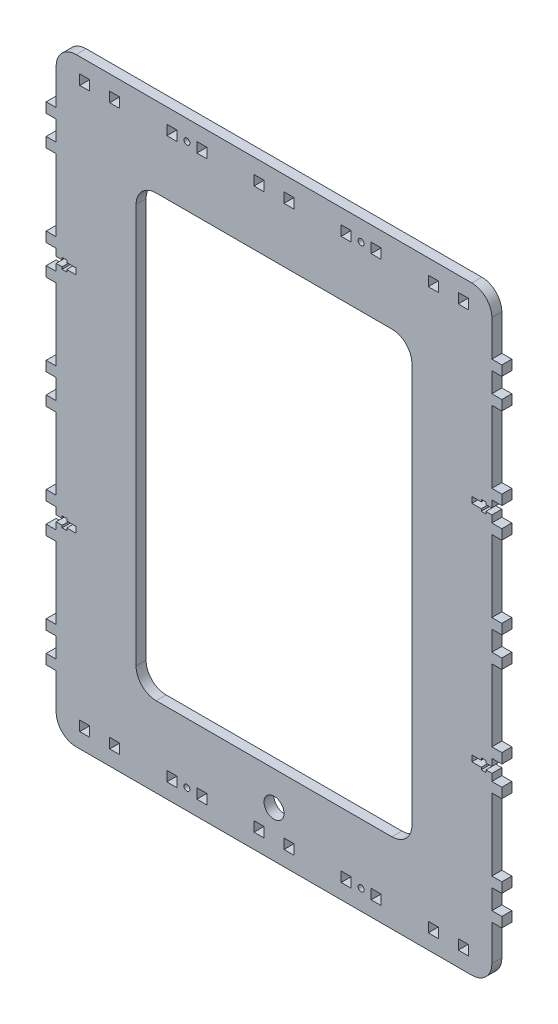
SolidWorks part; units mm, degrees
ref_plane "Front Plane" through (0, 0, 0) normal (0, 0, 1) x (1, 0, 0)
ref_plane "Top Plane" through (0, 0, 0) normal (0, 1, 0) x (1, 0, 0)
ref_plane "Right Plane" through (0, 0, 0) normal (1, 0, 0) x (0, 0, -1)
sketch "Sketch1" plane through (0, 0, 0) normal (0, 0, 1) x (1, 0, 0)
  line L0 (-109, -140) -> (109, -140) construction
  line L1 (109, 140) -> (109, 122)
  line L2 (-92.2, -140) -> (-82.2, -140) construction
  line L3 (-109, 140) -> (109, 140) construction
  line L5 (-92.2, -137.5) -> (-97.2, -137.5)
  line L6 (-92.2, -137.5) -> (-92.2, -142.5)
  line L7 (-99, -150) -> (99, -150)
  line L8 (-92.2, -142.5) -> (-97.2, -142.5)
  line L9 (-97.2, -137.5) -> (-97.2, -142.5)
  line L10 (-82.2, -137.5) -> (-77.2, -137.5)
  line L11 (-82.2, -137.5) -> (-82.2, -142.5)
  line L12 (-82.2, -142.5) -> (-77.2, -142.5)
  line L13 (-77.2, -137.5) -> (-77.2, -142.5)
  line L14 (-87.2, -140) -> (-87.2, -133.0276) construction
  line L15 (-48.6, -140) -> (-38.6, -140) construction
  line L16 (-109, -140) -> (-109, -122)
  line L17 (-99, 150) -> (99, 150)
  line L19 (-48.6, -137.5) -> (-53.6, -137.5)
  line L20 (-48.6, -137.5) -> (-48.6, -142.5)
  line L21 (-48.6, -142.5) -> (-53.6, -142.5)
  line L22 (-53.6, -137.5) -> (-53.6, -142.5)
  line L23 (-38.6, -137.5) -> (-33.6, -137.5)
  line L24 (-38.6, -137.5) -> (-38.6, -142.5)
  line L25 (-38.6, -142.5) -> (-33.6, -142.5)
  line L26 (-33.6, -137.5) -> (-33.6, -142.5)
  line L27 (-43.6, -140) -> (-43.6, -133.0276) construction
  line L28 (-5, -140) -> (5, -140) construction
  line L30 (-5, -137.5) -> (-10, -137.5)
  line L32 (-5, -137.5) -> (-5, -142.5)
  line L33 (-5, -142.5) -> (-10, -142.5)
  line L34 (-10, -137.5) -> (-10, -142.5)
  line L35 (5, -137.5) -> (10, -137.5)
  line L36 (5, -137.5) -> (5, -142.5)
  line L37 (5, -142.5) -> (10, -142.5)
  line L38 (10, -137.5) -> (10, -142.5)
  line L39 (0, -140) -> (0, -133.0276) construction
  line L40 (38.6, -140) -> (48.6, -140) construction
  line L41 (38.6, -137.5) -> (33.6, -137.5)
  line L42 (38.6, -137.5) -> (38.6, -142.5)
  line L43 (38.6, -142.5) -> (33.6, -142.5)
  line L44 (33.6, -137.5) -> (33.6, -142.5)
  line L45 (48.6, -137.5) -> (53.6, -137.5)
  line L46 (48.6, -137.5) -> (48.6, -142.5)
  line L47 (48.6, -142.5) -> (53.6, -142.5)
  line L48 (-109, -108) -> (-109, -117)
  line L49 (53.6, -137.5) -> (53.6, -142.5)
  line L50 (0, 182.823) -> (0, -174.5679) construction
  line L51 (43.6, -140) -> (43.6, -133.0276) construction
  line L52 (82.2, -140) -> (92.2, -140) construction
  line L53 (82.2, -137.5) -> (77.2, -137.5)
  line L54 (82.2, -137.5) -> (82.2, -142.5)
  line L55 (82.2, -142.5) -> (77.2, -142.5)
  line L56 (77.2, -137.5) -> (77.2, -142.5)
  line L57 (92.2, -137.5) -> (97.2, -137.5)
  line L58 (92.2, -137.5) -> (92.2, -142.5)
  line L59 (92.2, -142.5) -> (97.2, -142.5)
  line L60 (97.2, -137.5) -> (97.2, -142.5)
  line L61 (87.2, -140) -> (87.2, -133.0276) construction
  line L62 (-129.5738, 0) -> (-109, 0) construction
  line L63 (82.2, 140) -> (92.2, 140) construction
  line L64 (38.6, 140) -> (48.6, 140) construction
  line L65 (-5, 140) -> (5, 140) construction
  line L66 (-48.6, 140) -> (-38.6, 140) construction
  line L67 (-92.2, 140) -> (-82.2, 140) construction
  line L68 (97.2, 137.5) -> (97.2, 142.5)
  line L70 (92.2, 142.5) -> (97.2, 142.5)
  line L71 (92.2, 137.5) -> (92.2, 142.5)
  line L73 (92.2, 137.5) -> (97.2, 137.5)
  line L74 (77.2, 137.5) -> (77.2, 142.5)
  line L77 (82.2, 142.5) -> (77.2, 142.5)
  line L78 (82.2, 137.5) -> (82.2, 142.5)
  line L79 (82.2, 137.5) -> (77.2, 137.5)
  line L80 (53.6, 137.5) -> (53.6, 142.5)
  line L81 (48.6, 142.5) -> (53.6, 142.5)
  line L82 (48.6, 137.5) -> (48.6, 142.5)
  line L84 (48.6, 137.5) -> (53.6, 137.5)
  line L86 (33.6, 137.5) -> (33.6, 142.5)
  line L89 (38.6, 142.5) -> (33.6, 142.5)
  line L92 (38.6, 137.5) -> (38.6, 142.5)
  line L93 (38.6, 137.5) -> (33.6, 137.5)
  line L94 (10, 137.5) -> (10, 142.5)
  line L95 (5, 142.5) -> (10, 142.5)
  line L97 (5, 137.5) -> (5, 142.5)
  line L98 (5, 137.5) -> (10, 137.5)
  line L99 (-10, 137.5) -> (-10, 142.5)
  line L100 (-5, 142.5) -> (-10, 142.5)
  line L101 (-5, 137.5) -> (-5, 142.5)
  line L102 (-5, 137.5) -> (-10, 137.5)
  line L103 (-33.6, 137.5) -> (-33.6, 142.5)
  line L104 (-38.6, 142.5) -> (-33.6, 142.5)
  line L105 (-38.6, 137.5) -> (-38.6, 142.5)
  line L106 (-38.6, 137.5) -> (-33.6, 137.5)
  line L107 (-53.6, 137.5) -> (-53.6, 142.5)
  line L108 (-48.6, 142.5) -> (-53.6, 142.5)
  line L109 (-48.6, 137.5) -> (-48.6, 142.5)
  line L110 (-48.6, 137.5) -> (-53.6, 137.5)
  line L111 (-77.2, 137.5) -> (-77.2, 142.5)
  line L112 (-82.2, 142.5) -> (-77.2, 142.5)
  line L113 (-82.2, 137.5) -> (-82.2, 142.5)
  line L114 (-82.2, 137.5) -> (-77.2, 137.5)
  line L115 (-97.2, 137.5) -> (-97.2, 142.5)
  line L116 (-92.2, 142.5) -> (-97.2, 142.5)
  line L117 (-92.2, 137.5) -> (-92.2, 142.5)
  line L118 (-92.2, 137.5) -> (-97.2, 137.5)
  line L119 (109, 0) -> (97.7792, 0) construction
  line L120 (59, -110) -> (-59, -110)
  line L121 (69, -100) -> (69, 100)
  line L122 (59, 110) -> (-59, 110)
  line L123 (-69, -100) -> (-69, 100)
  line L124 (69, -110) -> (-69, 110) construction
  line L125 (69, 110) -> (-69, -110) construction
  line L126 (109, -1.5) -> (109, -5)
  line L127 (114, -5) -> (114, -10)
  line L128 (114, -10) -> (109, -10)
  line L129 (114, -5) -> (109, -5)
  line L130 (109, 1.5) -> (109, 5)
  line L131 (109, 5) -> (114, 5)
  line L132 (114, 5) -> (114, 10)
  line L133 (114, 10) -> (109, 10)
  line L134 (109, -1.5) -> (109, 1.5) construction
  line L135 (109, 5) -> (109, -5)
  line L136 (109, -10) -> (109, -46)
  line L137 (109, -51) -> (109, -54.5)
  line L138 (109, -66) -> (109, -102)
  line L139 (109, -57.5) -> (109, -61)
  line L140 (109, -122) -> (109, -140)
  line L141 (109, -107) -> (109, -117)
  line L142 (-109, 122) -> (-109, 140)
  line L143 (-109, 117) -> (-109, 107)
  line L144 (-109, 107) -> (-109, 117)
  line L145 (-109, 102) -> (-109, 66)
  line L146 (99, 0) -> (109, 0) construction
  line L147 (109, 56) -> (95.1587, 56) construction
  line L148 (109, 54.5) -> (109, 51)
  line L149 (114, 51) -> (114, 46)
  line L150 (114, 46) -> (109, 46)
  line L151 (114, 51) -> (109, 51)
  line L152 (109, 57.5) -> (109, 61)
  line L153 (109, 61) -> (114, 61)
  line L154 (114, 61) -> (114, 66)
  line L155 (114, 66) -> (109, 66)
  line L156 (109, 54.5) -> (109, 57.5) construction
  line L157 (109, 57.5) -> (106, 57.5)
  line L158 (103.7, 57.5) -> (103.7, 58.6)
  line L159 (106, 53.4) -> (103.7, 53.4)
  line L160 (106, 58.6) -> (106, 57.5)
  line L161 (103.7, 57.5) -> (99, 57.5)
  line L162 (99, 57.5) -> (99, 54.5)
  line L163 (99, 54.5) -> (103.7, 54.5)
  line L164 (106, 54.5) -> (106, 53.4)
  line L165 (103.7, 58.6) -> (106, 58.6)
  line L166 (103.7, 53.4) -> (103.7, 54.5)
  line L167 (106, 54.5) -> (109, 54.5)
  line L168 (99, 56) -> (109, 56) construction
  line L169 (109, 113.5) -> (109, 110.5)
  line L170 (109, 110.5) -> (109, 107)
  line L171 (114, 107) -> (114, 102)
  line L172 (114, 102) -> (109, 102)
  line L173 (114, 107) -> (109, 107)
  line L174 (109, 113.5) -> (109, 117)
  line L175 (109, 117) -> (114, 117)
  line L176 (114, 117) -> (114, 122)
  line L177 (114, 122) -> (109, 122)
  line L178 (109, 110.5) -> (109, 113.5) construction
  line L179 (109, 102) -> (109, 66)
  line L180 (-109, 66) -> (-109, 102)
  line L181 (-109, 61) -> (-109, 57.5)
  line L182 (-109, 51) -> (-109, 54.5)
  line L183 (-109, 46) -> (-109, 10)
  line L184 (-109, 54.5) -> (-109, 51)
  line L185 (-109, 57.5) -> (-109, 61)
  line L186 (-109, 10) -> (-109, 46)
  line L187 (-109, 5) -> (-109, -5)
  line L188 (-69, 0) -> (129.5738, 0) construction
  line L189 (-109, -5) -> (-109, 5)
  line L190 (-109, -10) -> (-109, -46)
  line L191 (-109, -46) -> (-109, -10)
  line L192 (109, -110.5) -> (109, -113.5) construction
  line L193 (81.3867, -112) -> (79.0545, -112) construction
  line L194 (-109, -51) -> (-109, -54.5)
  line L195 (-109, -61) -> (-109, -57.5)
  line L196 (99, -56) -> (95.1587, -56) construction
  line L197 (-109, -66) -> (-109, -102)
  line L198 (-109, -57.5) -> (-109, -61)
  line L199 (-109, -54.5) -> (-109, -51)
  line L200 (-109, -102) -> (-109, -66)
  line L201 (-109, -107) -> (-109, -117)
  line L202 (-109, -117) -> (-109, -107)
  line L203 (-109, -122) -> (-109, -150)
  line L204 (-109, -122) -> (-109, -140)
  line L205 (109, 102) -> (109, 66)
  line L206 (109, 61) -> (109, 51)
  line L207 (109, 46) -> (109, 10)
  line L208 (114, -122) -> (109, -122)
  line L209 (114, -117) -> (114, -122)
  line L210 (109, -117) -> (114, -117)
  line L211 (109, -113.5) -> (109, -117)
  line L212 (114, -107) -> (109, -107)
  line L213 (114, -102) -> (109, -102)
  line L214 (114, -107) -> (114, -102)
  line L215 (109, -110.5) -> (109, -107)
  line L216 (106, -54.5) -> (109, -54.5)
  line L217 (103.7, -53.4) -> (103.7, -54.5)
  line L218 (103.7, -58.6) -> (106, -58.6)
  line L219 (106, -54.5) -> (106, -53.4)
  line L220 (99, -54.5) -> (103.7, -54.5)
  line L221 (99, -57.5) -> (99, -54.5)
  line L222 (103.7, -57.5) -> (99, -57.5)
  line L223 (106, -58.6) -> (106, -57.5)
  line L224 (106, -53.4) -> (103.7, -53.4)
  line L225 (103.7, -57.5) -> (103.7, -58.6)
  line L226 (109, -57.5) -> (106, -57.5)
  line L227 (114, -66) -> (109, -66)
  line L228 (114, -61) -> (114, -66)
  line L229 (-109, -150) -> (69, 94.9541) construction
  line L230 (-109, 150) -> (109, -150) construction
  line L231 (109, -61) -> (114, -61)
  line L232 (109, -57.5) -> (109, -61)
  line L233 (114, -51) -> (109, -51)
  line L234 (114, -46) -> (109, -46)
  line L235 (114, -51) -> (114, -46)
  line L236 (109, -54.5) -> (109, -51)
  line L237 (-99, -56) -> (-95.1587, -56) construction
  line L241 (-109, -110.5) -> (-109, -113.5) construction
  line L244 (-109, 110.5) -> (-109, 113.5) construction
  line L248 (-99, 56) -> (-95.1587, 56) construction
  line L250 (-109, -1.5) -> (-109, 1.5) construction
  line L252 (-109, -54.5) -> (-109, -51)
  line L253 (-114, -51) -> (-114, -46)
  line L254 (-114, -46) -> (-109, -46)
  line L255 (-114, -51) -> (-109, -51)
  line L256 (-109, -57.5) -> (-109, -61)
  line L257 (-109, -61) -> (-114, -61)
  line L258 (-114, -61) -> (-114, -66)
  line L259 (-114, -66) -> (-109, -66)
  line L260 (-109, -57.5) -> (-106, -57.5)
  line L261 (-103.7, -57.5) -> (-103.7, -58.6)
  line L262 (-106, -53.4) -> (-103.7, -53.4)
  line L263 (-106, -58.6) -> (-106, -57.5)
  line L264 (-103.7, -57.5) -> (-99, -57.5)
  line L265 (-99, -57.5) -> (-99, -54.5)
  line L266 (-99, -54.5) -> (-103.7, -54.5)
  line L267 (-106, -54.5) -> (-106, -53.4)
  line L268 (-103.7, -58.6) -> (-106, -58.6)
  line L269 (-103.7, -53.4) -> (-103.7, -54.5)
  line L270 (-106, -54.5) -> (-109, -54.5)
  line L271 (-109, -110.5) -> (-109, -107)
  line L272 (-114, -107) -> (-114, -102)
  line L273 (-114, -102) -> (-109, -102)
  line L274 (-114, -107) -> (-109, -107)
  line L275 (-109, -113.5) -> (-109, -117)
  line L276 (-109, -117) -> (-114, -117)
  line L277 (-114, -117) -> (-114, -122)
  line L278 (-114, -122) -> (-109, -122)
  line L301 (-114, 122) -> (-109, 122)
  line L302 (-114, 117) -> (-114, 122)
  line L303 (-109, 117) -> (-114, 117)
  line L304 (-109, 113.5) -> (-109, 117)
  line L305 (-114, 107) -> (-109, 107)
  line L306 (-114, 102) -> (-109, 102)
  line L307 (-114, 107) -> (-114, 102)
  line L308 (-109, 110.5) -> (-109, 107)
  line L309 (-106, 54.5) -> (-109, 54.5)
  line L310 (-103.7, 53.4) -> (-103.7, 54.5)
  line L311 (-103.7, 58.6) -> (-106, 58.6)
  line L312 (-106, 54.5) -> (-106, 53.4)
  line L313 (-99, 54.5) -> (-103.7, 54.5)
  line L314 (-99, 57.5) -> (-99, 54.5)
  line L315 (-103.7, 57.5) -> (-99, 57.5)
  line L316 (-106, 58.6) -> (-106, 57.5)
  line L317 (-106, 53.4) -> (-103.7, 53.4)
  line L318 (-103.7, 57.5) -> (-103.7, 58.6)
  line L319 (-109, 57.5) -> (-106, 57.5)
  line L320 (-114, 66) -> (-109, 66)
  line L321 (-114, 61) -> (-114, 66)
  line L322 (-109, 61) -> (-114, 61)
  line L323 (-109, 57.5) -> (-109, 61)
  line L324 (-114, 51) -> (-109, 51)
  line L325 (-114, 46) -> (-109, 46)
  line L326 (-114, 51) -> (-114, 46)
  line L327 (-109, 54.5) -> (-109, 51)
  line L339 (-114, 10) -> (-109, 10)
  line L340 (-114, 5) -> (-114, 10)
  line L341 (-109, 5) -> (-114, 5)
  line L342 (-109, 1.5) -> (-109, 5)
  line L343 (-114, -5) -> (-109, -5)
  line L344 (-114, -10) -> (-109, -10)
  line L345 (-114, -5) -> (-114, -10)
  line L346 (-109, -1.5) -> (-109, -5)
  line L347 (-109, 150) -> (-109, 122)
  line L348 (109, 117) -> (109, 107)
  line L349 (101.7333, 140) -> (109, 150) construction
  circle A1 centre (0, -126.8749) radius 5
  circle A3 centre (-43.6, -140) radius 1.5
  circle A5 centre (43.6, -140) radius 1.5
  circle A7 centre (43.6, 140) radius 1.5
  circle A8 centre (-43.6, 140) radius 1.5
  arc A9 (-59, -110) -> (-69, -100) centre (-59, -100) cw
  arc A10 (69, -100) -> (59, -110) centre (59, -100) cw
  arc A11 (69, 100) -> (59, 110) centre (59, 100) ccw
  arc A12 (-59, 110) -> (-69, 100) centre (-59, 100) ccw
  arc A13 (-99, -150) -> (-109, -140) centre (-99, -140) cw
  arc A14 (109, -140) -> (99, -150) centre (99, -140) cw
  arc A15 (109, 140) -> (99, 150) centre (99, 140) ccw
  arc A16 (-99, 150) -> (-109, 140) centre (-99, 140) ccw
  point P39 (0, 0)
  point P292 (0, 0)
  dimension "D4" = 10
  dimension "D5" = 43.6
  dimension "D3" = 280
  dimension "D7" = 43.6
  dimension "D10" = 10
  dimension "D14" = 3
  dimension "D18" = 5
  dimension "D22" = 3
  dimension "D26" = 5
  dimension "D31" = 10
  dimension "D1" = 218
  dimension "D2" = 10
  dimension "D6" = 43.6
  dimension "D8" = 43.6
  dimension "D9" = 5
  dimension "D11" = 5
  dimension "D12" = 10
  dimension "D13" = 5
  dimension "D15" = 5
  dimension "D16" = 10
  dimension "D17" = 5
  dimension "D19" = 5
  dimension "D20" = 10
  dimension "D21" = 5
  dimension "D23" = 5
  dimension "D24" = 10
  dimension "D25" = 5
  dimension "D27" = 5
  dimension "D28" = 10
  dimension "D29" = 40
  dimension "D30" = 40
  dimension "D34" = 10
  dimension "D35" = 5
  dimension "D36" = 5
  dimension "D37" = 5.2
  dimension "D38" = 3
  dimension "D39" = 2.3
  dimension "D40" = 3
  dimension "D41" = 10
  dimension "D42" = 10
  dimension "D43" = 5
  dimension "D44" = 5
  dimension "D50" = 56
extrude "Boss-Extrude5" add sketch "Sketch1" along normal blind 5 contours L343 L345 L344 L190 L254 L253 L255 L194 L270 L267 L262 L269 L266 L265 L264 L261 L268 L263 L260 L195 L257 L258 L259 L197 L273 L272 L274 L201 L48 L202 L276 L277 L278 L203 L16 L7 L140 L208 L209 L210 L141 L212 L214 L213 L138 L227 L228 L231 region at (105.2319, 131, 0)
